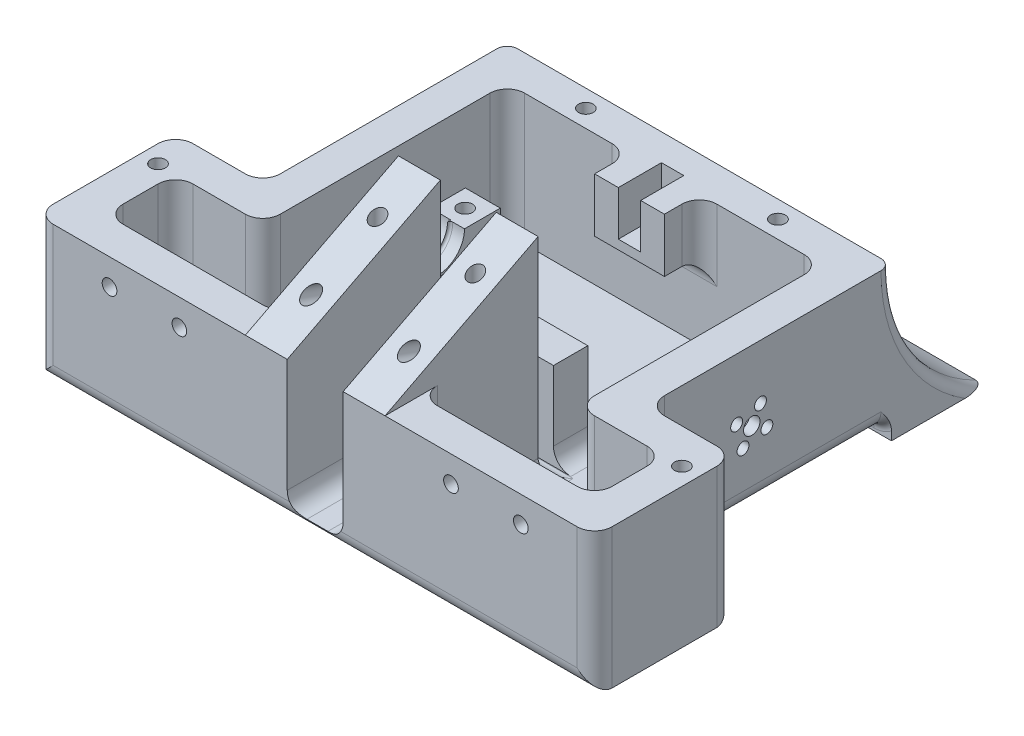
SolidWorks part; units mm, degrees
other "Markup1"
sketch "Sketch18" plane through (114.3, 30, 116.3209) normal (0.4263, 0.8263, 0.3681) x (0.7378, -0.0822, -0.67)
ref_plane "Front Plane" through (0, 0, 0) normal (0, 0, 1) x (1, 0, 0)
ref_plane "Top Plane" through (0, 0, 0) normal (0, 1, 0) x (1, 0, 0)
ref_plane "Right Plane" through (0, 0, 0) normal (1, 0, 0) x (0, 0, -1)
ref_plane "Plane2" through (14, 0, 0) normal (1, 0, 0) x (0, 0, -1)
sketch "Sketch1" plane through (0, 0, 0) normal (0, 1, 0) x (1, 0, 0)
  line L1 (55, 0) -> (80, 0)
  line L4 (0, 70) -> (55, 70)
  line L5 (55, 0) -> (55, 70)
  line L8 (0, -55) -> (0, 55) construction
  line L9 (0, 70) -> (0, -40)
  line L10 (0, -40) -> (80, -40)
  line L12 (80, 0) -> (80, -40)
  point P13 (80, -40)
  dimension "D1" = 55
  dimension "D2" = 70
  dimension "D3" = 25
  dimension "D4" = 40
extrude "Boss-Extrude2" add sketch "Sketch1" along normal blind 40 contours L4 L5 L1 L12 L10 L9
sketch "Sketch2" plane through (0, 40, 0) normal (0, 1, 0) x (1, 0, 0)
  line L0 (70, -10) -> (45, -10)
  line L1 (45, -10) -> (45, 60)
  line L2 (45, 60) -> (10, 60)
  line L3 (10, 60) -> (10, -30)
  line L4 (10, -30) -> (70, -30)
  line L5 (70, -30) -> (70, -10)
  line L6 (80, 0) -> (55, 0)
  line L7 (80, -40) -> (80, 0)
  line L8 (0, -40) -> (80, -40)
  line L9 (0, 70) -> (0, -40)
  line L10 (55, 70) -> (0, 70)
  line L11 (55, 0) -> (55, 70)
  line L12 (80, 0) -> (55, 0)
  line L13 (80, -40) -> (80, 0)
  line L14 (0, -40) -> (80, -40)
  line L15 (0, 70) -> (0, -40)
  line L16 (55, 70) -> (0, 70)
  line L17 (55, 0) -> (55, 70)
  dimension "D1" = 0
  dimension "D2" = 10
extrude "Cut-Extrude1" cut sketch "Sketch2" against normal blind 37.46 contours L0 L1 L2 L3 L4 L5
sketch "Sketch34" plane through (55, 0, 0) normal (1, 0, 0) x (0, 0, -1)
  line L0 (70, 40) -> (70, -3.71)
  line L3 (70, -3.71) -> (97.1385, -3.71)
  arc A1 (70, 40) -> (97.1385, -3.71) centre (118.7695, 40) ccw
  dimension "D1" = 43.71
  dimension "D2" = 27.1385
extrude "Boss-Extrude9" add sketch "Sketch34" against normal up to vertex (45 mm away) up to point (10, 40, -60)
sketch "Sketch36" plane through (0, 40, 0) normal (0, 1, 0) x (1, 0, 0)
  line L0 (27.5, 60) -> (27.5, 70) construction
  line L1 (45, 60) -> (10, 60) construction
  line L2 (10, 70) -> (55, 70) construction
  line L3 (22.5487, 65) -> (32.4513, 65) construction
  line L8 (70, -10) -> (80, -10) construction
  line L11 (80, 0) -> (80, -40) construction
  line L12 (75, -10) -> (75, -21.6952) construction
  circle A0 centre (27.5, 65) radius 2.1
  circle A8 centre (75, -10) radius 2.1
  point P11 (27.5, 65)
  dimension "D1" = 4.2
  dimension "D5" = 4.2
extrude "Cut-Extrude18" cut sketch "Sketch36" against normal blind 8
sketch "Sketch37" plane through (0, 0, 40) normal (0, 0, 1) x (1, 0, 0)
  line L0 (40, 40) -> (40, 32.5) construction
  line L1 (0, 40) -> (80, 40) construction
  line L2 (40, 32.5) -> (38.88, 32.5) construction
  circle A0 centre (38.88, 32.5) radius 2.1
  circle A2 centre (58.88, 32.5) radius 2.1
  dimension "D3" = 4.2
  dimension "D1" = 7.5
  dimension "D2" = 1.12
  dimension "D4" = 2
extrude "Cut-Extrude19" cut sketch "Sketch37" against normal blind 7
mirror "Mirror1" about plane through (0, 0, 0) normal (1, 0, 0) of bodies 152 114
sketch "Sketch17" plane through (0, 40, 0) normal (0, 1, 0) x (1, 0, 0)
  line L0 (0, -94.6286) -> (0, 94.6286) construction
  line L14 (10, 60) -> (10, -30) construction
  line L15 (-10, 60) -> (-10, -30) construction
  line L16 (10, 50) -> (10, -30)
  line L17 (-10, 50) -> (-10, -30)
  line L23 (-10, 50) -> (10, 50)
  line L24 (-10, -30) -> (-20, -30)
  line L25 (0, 50) -> (0, -40) construction
  line L26 (-10, -30) -> (-70, -30) construction
  line L27 (10, -30) -> (20, -30)
  line L28 (10, -30) -> (70, -30) construction
  line L29 (-20, -30) -> (-20, -40)
  line L30 (-80, -40) -> (80, -40) construction
  line L31 (-20, -40) -> (20, -40)
  line L32 (20, -40) -> (20, -30)
  dimension "D1" = 90
extrude "Cut-Extrude7" cut sketch "Sketch17" against normal up to surface (37.46 mm away)
sketch "Sketch27" plane through (0, 0, -50) normal (0, 0, 1) x (1, 0, 0)
  line L0 (10, 24.54) -> (-10, 24.54)
  line L3 (10, 2.54) -> (10, 40) construction
  line L4 (10, 2.54) -> (10, 24.54)
  line L5 (-10, 2.54) -> (-10, 40) construction
  line L6 (-10, 2.54) -> (-10, 24.54)
  line L7 (10, 2.54) -> (-10, 2.54) construction
  line L8 (10, 2.54) -> (-10, 2.54)
  dimension "D1" = 22
extrude "Cut-Extrude11" cut sketch "Sketch27" against normal up to surface (10 mm away) up to face at (27.5, 21.27, -60)
sketch "Sketch28" plane through (0, 40, 0) normal (0, 1, 0) x (1, 0, 0)
  line L1 (0, 56) -> (0, 70) construction
  line L2 (-10, 70) -> (10, 70) construction
  line L3 (-3.2, 49.65) -> (3.2, 49.65)
  line L4 (-3.2, 49.65) -> (-3.2, 62.35)
  line L5 (-3.2, 62.35) -> (3.2, 62.35)
  line L6 (3.2, 49.65) -> (3.2, 62.35)
  line L7 (-3.2, 49.65) -> (3.2, 62.35) construction
  line L8 (-3.2, 62.35) -> (3.2, 49.65) construction
  dimension "D1" = 14
  dimension "D2" = 6.4
  dimension "D3" = 12.7
extrude "Cut-Extrude12" cut sketch "Sketch28" against normal blind 12.8
sketch "Sketch20" [suppressed] plane through (0, 2.54, 0) normal (0, 1, 0) x (1, 0, 0)
  line L0 (0, -32.5) -> (0, -40) construction
  line L2 (0, -36.4375) -> (0, 36.4375) construction
  line L3 (0, -32.5) -> (14, -32.5) construction
  line L5 (20, -40) -> (-20, -40) construction
  circle A0 centre (14, -32.5) radius 1.52
  dimension "D3" = 3.04
  dimension "D1" = 7.5
  dimension "D2" = 14
extrude "Cut-Extrude10" [suppressed] cut sketch "Sketch20" against normal up to surface (2.54 mm away)
pattern_linear "LPattern1" [suppressed] count 4 spacing 10 count 2 spacing 28
sketch "Sketch5" plane through (45, 0, 0) normal (-1, 0, 0) x (0, 0, 1)
  line L0 (-30, 40) -> (-30, 20) construction
  line L1 (10, 40) -> (-60, 40) construction
  line L2 (-30, 20) -> (-60, 20) construction
  line L3 (-60, 2.54) -> (-60, 40) construction
  line L4 (-30, 20) -> (-32.5, 24.3301) construction
  circle A0 centre (-30, 20) radius 2.35
  circle A1 centre (-32.5, 24.3301) radius 1.7
  point P19 (-47.5, 15)
  dimension "D3" = 4.7
  dimension "D6" = 3.4
  dimension "D1" = 20
  dimension "D2" = 30
  dimension "D4" = 60
  dimension "D5" = 5
extrude "Cut-Extrude13" cut sketch "Sketch5" against normal up to surface (10 mm away) up to face at (55, 11.4517, -50.151)
pattern_circular "CirPattern1" count 4 over 360 about axis through (0, 20, -30) along (1, 0, 0) of "Cut-Extrude13"
sketch "Sketch29" plane through (-45, 0, 0) normal (-1, 0, 0) x (0, 0, 1)
  line L0 (-30, 20) -> (-60, 20) construction
  line L1 (-30, 40) -> (-30, 20) construction
  line L2 (-30, 20) -> (-34.3301, 22.5) construction
  line L3 (-30, 20) -> (-60, 20) construction
  line L4 (-30, 40) -> (-30, 20) construction
  circle A0 centre (-34.3301, 22.5) radius 1.7
  circle A1 centre (-30, 20) radius 2.35 construction
  circle A3 centre (-30, 20) radius 2.35
  dimension "D3" = 3.4
  dimension "D1" = 30
  dimension "D2" = 5
extrude "Cut-Extrude14" cut sketch "Sketch29" along a picked direction on the side of the normal up to surface (10 mm away) contours A0 | A3
pattern_circular "CirPattern2" count 4 over 360 about axis through (0, 20, -30) along (1, 0, 0) of "Cut-Extrude14"
sketch "Sketch31" plane through (45, 0, 0) normal (-1, 0, 0) x (0, 0, 1)
  circle A0 centre (-30, 20) radius 8
  dimension "D1" = 16
extrude "Cut-Extrude16" cut sketch "Sketch31" against normal blind 7
mirror "Mirror2" about plane through (0, 0, 0) normal (1, 0, 0) of "Cut-Extrude16"
sketch "Sketch32" plane through (-45, 0, 0) normal (1, 0, 0) x (0, 0, -1)
  line L0 (22, 20) -> (12, 20)
  line L1 (12, 20) -> (12, 2.54)
  line L3 (-10, 2.54) -> (60, 2.54) construction
  line L12 (30, 40) -> (30, 20) construction
  line L14 (60, 40) -> (30, 40) construction
  line L15 (-10, 40) -> (60, 40) construction
  line L16 (12, 2.54) -> (48, 2.54)
  line L17 (48, 20) -> (48, 2.54)
  line L18 (38, 20) -> (48, 20)
  line L19 (38, 20) -> (22, 20)
  point P17 (30, 20)
  dimension "D1" = 8
  dimension "D2" = 30
  dimension "D3" = 10
  dimension "D4" = 20
ref_plane "Plane1" through (0, 20, 0) normal (0, 1, 0) x (1, 0, 0)
sketch "Sketch33" plane through (0, 20, 0) normal (0, 1, 0) x (1, 0, 0)
  line L0 (-45, 38) -> (-39.77, 38)
  line L4 (-39.77, 38) -> (-39.77, 37.9817)
  line L5 (-39.77, 30) -> (-39.77, 38) construction
  line L6 (-39.77, 37.9817) -> (-39.1, 37.9817)
  line L7 (-39.1, 30) -> (-39.1, 38) construction
  line L8 (-39.1, 37.9817) -> (-39.1, 36.988)
  line L9 (-38.338, 37.75) -> (-34.5835, 37.75)
  line L10 (-12.29, 37.75) -> (-38.338, 37.75) construction
  line L11 (-34.5835, 37.75) -> (-34.5835, 30)
  line L12 (-34.5835, 30) -> (-45, 30)
  line L13 (-45, 30) -> (-45, 38)
  arc A1 (-39.1, 36.988) -> (-38.338, 37.75) centre (-38.338, 36.988) cw
  dimension "D1" = 10.4165
extrude "Boss-Extrude8" add sketch "Sketch32" along normal blind 10
revolve "Cut-Revolve1" cut sketch "Sketch33" angle 180 about L12
sketch "Sketch35" plane through (0, 20, 0) normal (0, 1, 0) x (1, 0, 0)
  line L0 (-45, 17) -> (-35, 17.125) construction
  line L1 (-45, 22) -> (-45, 12) construction
  line L2 (-35, 22.25) -> (-35, 12) construction
  line L3 (-35, 30) -> (-49.6292, 30) construction
  line L4 (-35, 12) -> (-35, 48) construction
  circle A0 centre (-40, 17.0625) radius 2.1
  circle A1 centre (-40, 42.9375) radius 2.1
  dimension "D1" = 4.2
extrude "Cut-Extrude17" cut sketch "Sketch35" against normal blind 10
mirror "Mirror4" about plane through (0, 0, 0) normal (1, 0, 0) of "Cut-Extrude17", "Cut-Revolve1", "Boss-Extrude8"
fillet "Fillet1" radius 5 11 edges at (-55, 0, -35) (55, 0, -35) (-80, 20, 40) (-80, 20, 0) (80, 20, 40) (80, 20, 0) (-67.5, 0, 0) (67.5, 0, 0) (0, 0, 40) (55, 20, 0) (-55, 20, 0)
fillet "Fillet2" radius 5 17 edges at (45, 21.27, 10) (-45, 21.27, 10) (10, 32.27, -60) (-10, 32.27, -60) (0, 24.54, -60) (40, 2.54, -48) (35, 2.54, -30) (40, 2.54, -12) (-40, 2.54, -48) (-40, 2.54, -12) (-35, 2.54, -30) (45, 21.27, -60) (-45, 21.27, -60) (70, 21.27, 30) (-70, 21.27, 30) (-70, 21.27, 10) (70, 21.27, 10)
fillet "Fillet3" radius 3 6 edges at (-53.5355, 1.4645, -70) (53.5355, 1.4645, -70) (-55, 14.2752, -77.3364) (55, 14.2752, -77.3364) (-30, 0, -70) (30, 0, -70)
sketch "Sketch38" plane through (20, 0, 0) normal (-1, 0, 0) x (0, 0, 1)
  line L2 (20, 0) -> (20, 2.54) construction
  line L4 (39.353, 2.54) -> (-3.837, 2.54)
  line L5 (-3.837, 2.54) -> (-3.837, 62.54)
  line L9 (5, 0) -> (35, 0) construction
  line L10 (-3.837, 62.54) -> (40, 40)
  line L11 (40, 40) -> (40, 5) construction
  line L12 (40, 40) -> (40, 5)
  arc A2 (35, 0) -> (40, 5) centre (35, 5) ccw construction
  arc A3 (39.353, 2.54) -> (40, 5) centre (35, 5) ccw
  dimension "D1" = 2.54
  dimension "D2" = 43.19
  dimension "D3" = 60
extrude "Boss-Extrude10" add sketch "Sketch38" along normal blind 12
mirror "Mirror5" about plane through (0, 0, 0) normal (1, 0, 0) of "Boss-Extrude10"
sketch "Sketch39" plane through (0, 2.54, 0) normal (0, 1, 0) x (1, 0, 0)
  line L0 (0, 13.9632) -> (0, 0) construction
  line L1 (-19.177, 9.0456) -> (19.177, 9.0456)
  line L2 (-19.177, 9.0456) -> (-19.177, 18.8809)
  line L3 (-19.177, 18.8809) -> (19.177, 18.8809)
  line L4 (19.177, 9.0456) -> (19.177, 18.8809)
  line L5 (-19.177, 9.0456) -> (19.177, 18.8809) construction
  line L6 (-19.177, 18.8809) -> (19.177, 9.0456) construction
  point P0 (0, 13.9632)
  dimension "D1" = 13.9632
  dimension "D2" = 38.354
  dimension "D3" = 9.8353
extrude "Boss-Extrude11" add sketch "Sketch39" along normal blind 25
sketch "Sketch40" plane through (14, 0, 0) normal (1, 0, 0) x (0, 0, -1)
  line L1 (-6.0465, 57.4581) -> (-6.0465, 48.4581)
  line L4 (-8.1465, 68.5936) -> (-8.1465, 42.5518) construction
  line L5 (-5.2465, 68.5935) -> (-11.0465, 68.5936) construction
  line L7 (-6.0465, 48.4581) -> (-8.1465, 48.4581)
  line L20 (-6.0465, 57.4581) -> (-8.1465, 57.4581)
  line L21 (-8.1465, 57.4581) -> (-8.1465, 48.4581)
  dimension "D1" = 11.1355
  dimension "D2" = 9
  dimension "D3" = 2.1
revolve "Cut-Revolve2" cut sketch "Sketch40" angle 360 about L4
sketch "Sketch41" plane through (14, 0, 0) normal (1, 0, 0) x (0, 0, -1)
  line L0 (-64.8562, 60.3169) -> (-11.4893, 40.893) construction
  line L5 (-18.3441, 45.6227) -> (-19.0623, 43.6493)
  line L6 (-19.0623, 43.6493) -> (-28.6844, 47.1514)
  line L8 (-29.6204, 49.7269) -> (-30.3386, 47.7536)
  line L9 (-30.3386, 47.7536) -> (-28.6844, 47.1514)
  line L10 (-29.6204, 49.7269) -> (-18.3441, 45.6227)
  point P3 (-38.1728, 50.6049)
  dimension "D1" = 8.3369
  dimension "D2" = 2.1
  dimension "D3" = 12
revolve "Cut-Revolve3" cut sketch "Sketch41" angle 360 about L0
mirror "Mirror7" about plane through (0, 0, 0) normal (1, 0, 0) of "Cut-Revolve3", "Cut-Revolve2"
fillet "Fillet4" radius 5 11 edges at (20, 21.27, 30) (20, 2.54, 13.0815) (8, 2.54, 17.758) (-8, 2.54, 17.758) (-20, 2.54, 13.0815) (-20, 21.27, 30) (-14, 2.54, -3.837) (14, 2.54, -3.837) (-19.177, 2.54, -13.9632) (19.177, 2.54, -13.9632) (0, 2.54, -18.8809)
